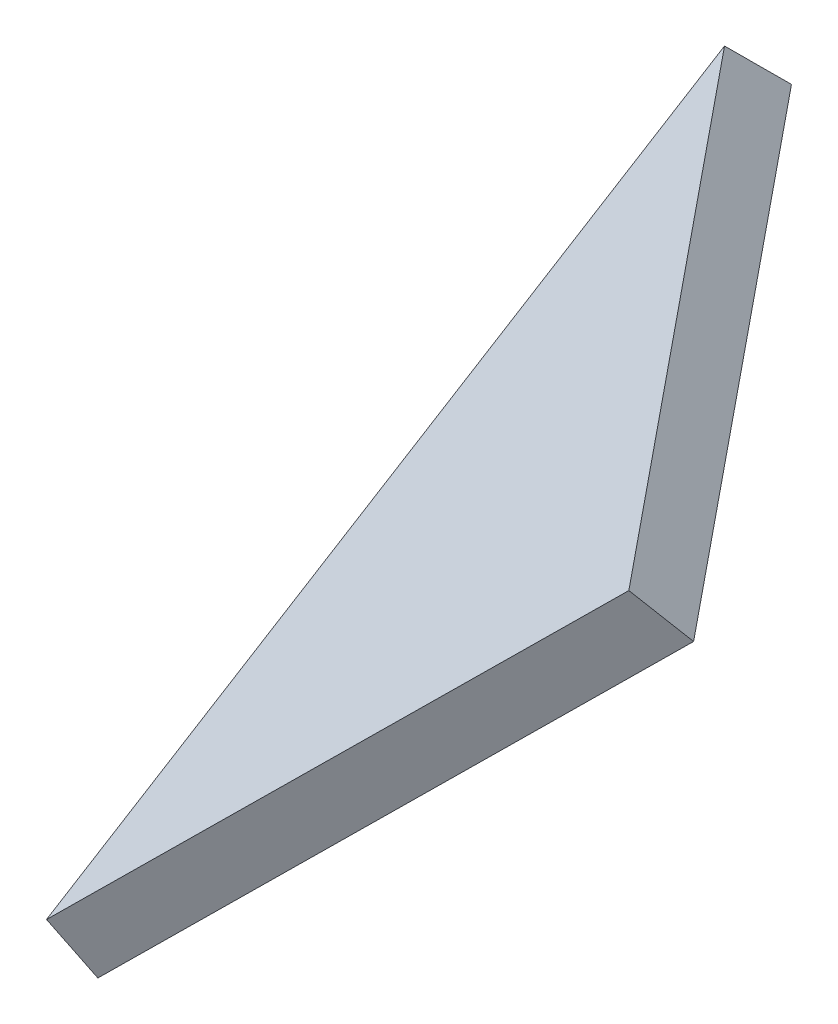
SolidWorks part; units mm, degrees
ref_plane "Front Plane" through (0, 0, 0) normal (0, 0, 1) x (1, 0, 0)
ref_plane "Top Plane" through (0, 0, 0) normal (0, 1, 0) x (1, 0, 0)
ref_plane "Right Plane" through (0, 0, 0) normal (1, 0, 0) x (0, 0, -1)
ref_plane "Plane1" through (-1433.12, 1495.8397, 1008.7401) normal (-0.622, 0.6492, 0.4378) x (0.7358, 0.2934, 0.6103)
sketch "Sketch1" plane through (-1433.12, 1495.8397, 1008.7401) normal (-0.622, 0.6492, 0.4378) x (0.7358, 0.2934, 0.6103)
  line L0 (-160.176, 64.6579) -> (-851.7875, -622.2401)
  line L1 (-851.7875, -622.2401) -> (-1100.8529, 320.162)
  line L2 (-1100.8529, 320.162) -> (-160.176, 64.6579)
  point P5 (-851.7875, -622.2401)
  point P9 (-1100.8529, 320.162)
extrude "Boss-Extrude1" add sketch "Sketch1" along normal blind 70
chamfer "Chamfer1" distance 70 angle 5.18 1 edges at (-1923.6194, 1197.1728, 914.6634) first distance on face at (-1901.8499, 1174.4506, 899.3404)
chamfer "Chamfer2" distance 70 angle 5.18 1 edges at (-1891.4477, 1490.9228, 524.774) first distance on face at (-1868.5059, 1468.3825, 510.8468)
chamfer "Chamfer3" distance 70 angle 5.18 1 edges at (-2235.5104, 1148.8047, 543.283) first distance on face at (-2213.7409, 1126.0825, 527.96)
equation "\"D1@Boss-Extrude1\" = \"wall_thick@4Vcorrection.Assembly\""
equation "\"C\"= \"C@4Vcorrection.Assembly\""
equation "\"Thick\"= \"wall_thick@4Vcorrection.Assembly\""
equation "\"D1@Chamfer1\"=\"Thick\""
equation "\"D2@Chamfer1\"=\"C\""
equation "\"D2@Chamfer2\"=\"C\""
equation "\"D1@Chamfer2\"=\"Thick\""
equation "\"D1@Chamfer3\"=\"Thick\""
equation "\"D2@Chamfer3\"=\"C\""
